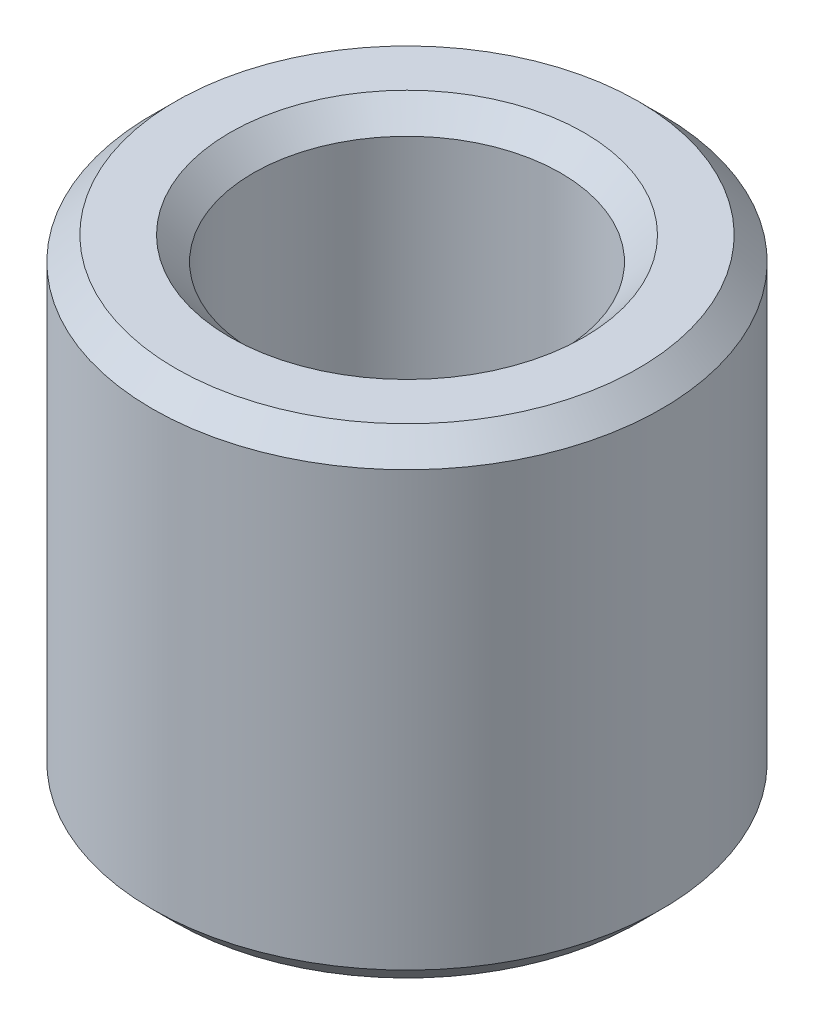
SolidWorks part; units mm, degrees
ref_plane "Front Plane" through (0, 0, 0) normal (0, 0, 1) x (1, 0, 0)
ref_plane "Top Plane" through (0, 0, 0) normal (0, 1, 0) x (1, 0, 0)
ref_plane "Right Plane" through (0, 0, 0) normal (1, 0, 0) x (0, 0, -1)
sketch "Sketch1" plane through (0, 0, 0) normal (0, 1, 0) x (1, 0, 0)
  circle A0 centre (0, 0) radius 20
  dimension "SLEEVE_OD" = 40
extrude "Boss-Extrude1" add sketch "Sketch1" along normal blind 37.6945
sketch "Sketch2" plane through (0, 0, 0) normal (0, 1, 0) x (1, 0, 0)
  circle A0 centre (0, 0) radius 12.0773
  dimension "BORE_D" = 24.1545
extrude "Cut-Extrude1" cut sketch "Sketch2" along normal through all
chamfer "Chamfer1" distance 1.8329 angle 45 4 edges at (0, 37.6945, 12.0773) (0, 0, 12.0773) (0, 0, 20) (0, 37.6945, 20)
